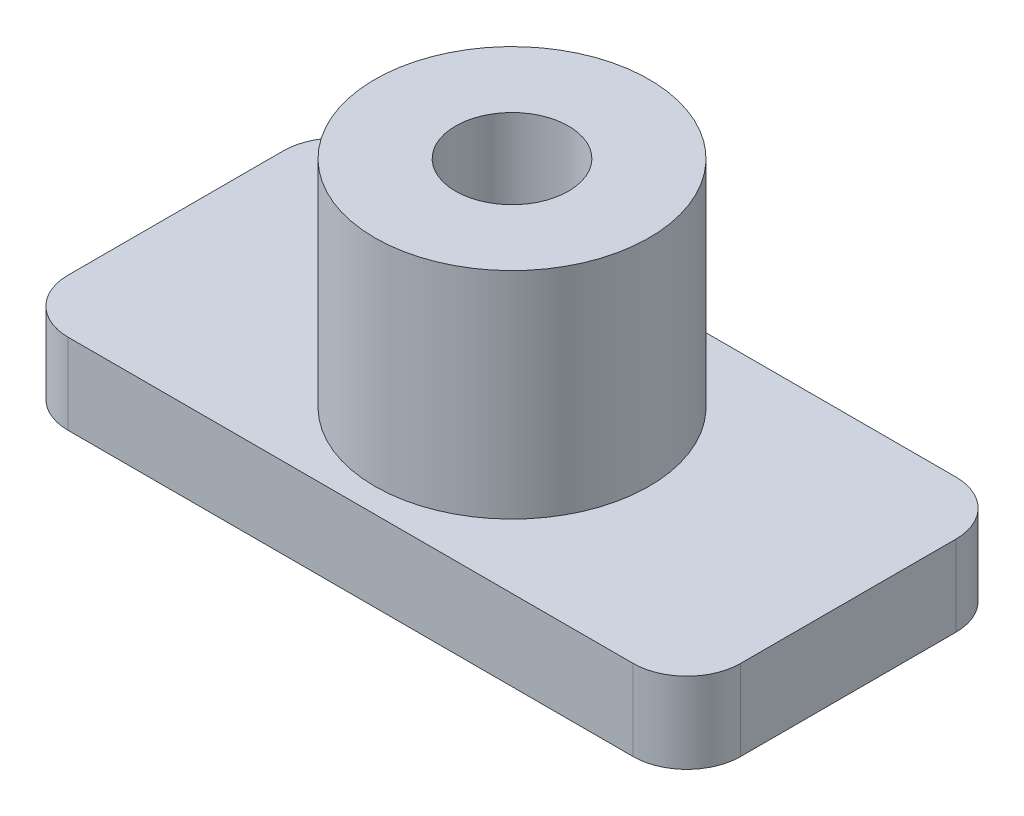
SolidWorks part; units mm, degrees
ref_plane "Front Plane" through (0, 0, 0) normal (0, 0, 1) x (1, 0, 0)
ref_plane "Top Plane" through (0, 0, 0) normal (0, 1, 0) x (1, 0, 0)
ref_plane "Right Plane" through (0, 0, 0) normal (1, 0, 0) x (0, 0, -1)
sketch "Sketch1" plane through (0, 0, 0) normal (0, 1, 0) x (1, 0, 0)
  line L1 (12.5, -6) -> (-12.5, -6)
  line L2 (12.5, -6) -> (12.5, 6)
  line L3 (12.5, 6) -> (-12.5, 6)
  line L4 (-12.5, -6) -> (-12.5, 6)
  line L5 (12.5, -6) -> (-12.5, 6) construction
  line L6 (12.5, 6) -> (-12.5, -6) construction
  point P0 (0, 0)
  dimension "D1" = 25
  dimension "D2" = 12
extrude "Boss-Extrude1" add sketch "Sketch1" along normal blind 3
sketch "Sketch2" plane through (0, 3, 0) normal (0, 1, 0) x (1, 0, 0)
  circle A0 centre (0, 0) radius 5.1
  circle A1 centre (0, 0) radius 2.1
  dimension "D1" = 3
  dimension "D2" = 4.2
extrude "Boss-Extrude2" add sketch "Sketch2" along normal blind 8
fillet "Fillet1" radius 2 4 edges at (12.5, 1.5, -6) (12.5, 1.5, 6) (-12.5, 1.5, -6) (-12.5, 1.5, 6)
